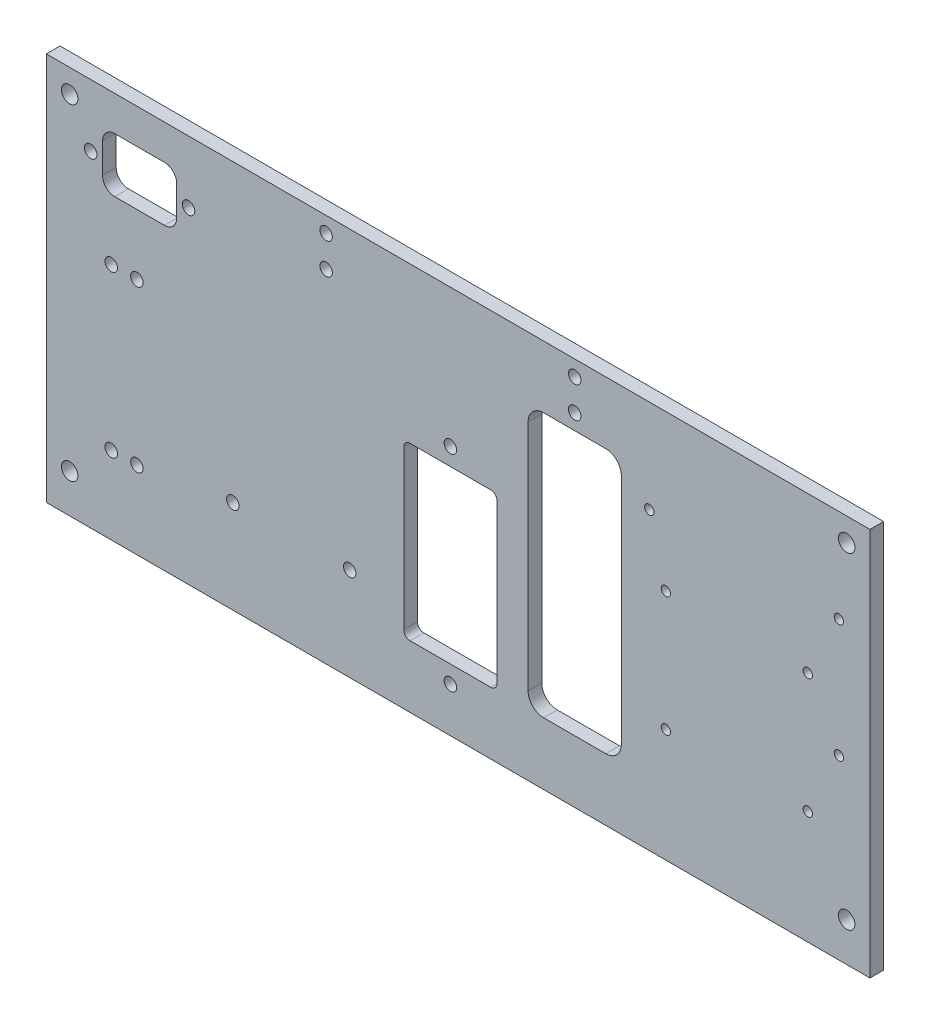
SolidWorks part; units mm, degrees
material "Acrylic (Medium-high impact)"
ref_plane "Front Plane" through (0, 0, 0) normal (0, 0, 1) x (1, 0, 0)
ref_plane "Top Plane" through (0, 0, 0) normal (0, 1, 0) x (1, 0, 0)
ref_plane "Right Plane" through (0, 0, 0) normal (1, 0, 0) x (0, 0, -1)
sketch "Sketch1" plane through (0, 0, 0) normal (0, 0, 1) x (1, 0, 0)
  line L1 (-168.275, 79.375) -> (168.275, 79.375)
  line L2 (-168.275, 79.375) -> (-168.275, -79.375)
  line L3 (-168.275, -79.375) -> (168.275, -79.375)
  line L4 (168.275, 79.375) -> (168.275, -79.375)
  line L5 (-168.275, 79.375) -> (168.275, -79.375) construction
  line L6 (-168.275, -79.375) -> (168.275, 79.375) construction
  point P0 (0, 0)
  dimension "D1" = 158.75
  dimension "D2" = 336.55
extrude "Boss-Extrude1" add sketch "Sketch1" along normal blind 5.588 contours L1 L4 L3 L2
hole_wizard "1/4 Clearance Hole1" positions "Sketch3" profile "Sketch2" hole size "1/4" standard "ANSI Inch" end condition up to next
sketch "Sketch3" plane through (0, 0, 0) normal (0, 0, -1) x (-1, 0, 0)
  line L1 (-158.75, 69.85) -> (158.75, 69.85) construction
  line L2 (-158.75, 69.85) -> (-158.75, -63.5) construction
  line L3 (-158.75, -63.5) -> (158.75, -63.5) construction
  line L4 (158.75, 69.85) -> (158.75, -63.5) construction
  line L5 (168.275, 79.375) -> (-168.275, 79.375) construction
  line L6 (-168.275, 79.375) -> (-168.275, -79.375) construction
  line L10 (168.275, 79.375) -> (168.275, -79.375) construction
  line L11 (168.275, -79.375) -> (-168.275, -79.375) construction
  point P1 (-158.75, 69.85)
  point P2 (158.75, -63.5)
  point P283 (-158.75, -63.5)
  point P284 (158.75, 69.85)
  dimension "D1" = 9.525
  dimension "D2" = 9.525
  dimension "D3" = 9.525
  dimension "D4" = 15.875
sketch "Sketch2" plane through (158.75, 69.85, 0) normal (1, 0, 0) x (0, 1, 0)
  line L0 (0, 0) -> (0, 5.588)
  line L1 (0, 5.588) -> (3.3782, 5.588)
  line L2 (3.3782, 5.588) -> (3.3782, 0)
  line L5 (3.3782, 0) -> (0, 0)
  line L11 (0, -6.35) -> (0, 107.95) construction
  dimension "Thru Hole Dia." = 6.7564
  dimension "Thru Hole Depth" = 5.588
hole_wizard "#6 Clearance Hole1" positions "Sketch6" profile "Sketch7" hole size "#6" standard "ANSI Inch" end condition up to next
sketch "Sketch6" plane through (0, 0, 0) normal (0, 0, -1) x (-1, 0, 0)
  line L1 (-155.575, 41.275) -> (-78.105, 41.275) construction
  line L2 (-155.575, 41.275) -> (-155.575, -6.985) construction
  line L3 (-155.575, -6.985) -> (-78.105, -6.985) construction
  line L4 (-78.105, 41.275) -> (-78.105, -6.985) construction
  line L5 (-168.275, 79.375) -> (-168.275, -79.375) construction
  line L6 (168.275, 79.375) -> (-168.275, 79.375) construction
  point P0 (-155.575, 41.275)
  point P105 (-155.575, -6.985)
  point P106 (-78.105, 41.275)
  dimension "D1" = 77.47
  dimension "D2" = 48.26
  dimension "D3" = 12.7
  dimension "D4" = 38.1
sketch "Sketch7" plane through (155.575, 41.275, 0) normal (1, 0, 0) x (0, 1, 0)
  line L0 (0, 0) -> (0, 5.588)
  line L1 (0, 5.588) -> (1.8986, 5.588)
  line L2 (1.8986, 5.588) -> (1.8986, 0)
  line L5 (1.8986, 0) -> (0, 0)
  line L11 (0, -6.35) -> (0, 107.95) construction
  dimension "Thru Hole Dia." = 3.7973
  dimension "Thru Hole Depth" = 5.588
hole_wizard "#6 Clearance Hole2" positions "Sketch9" profile "Sketch10" hole size "#6" standard "ANSI Inch" end condition up to next
sketch "Sketch9" plane through (0, 0, 0) normal (0, 0, -1) x (-1, 0, 0)
  line L1 (-142.875, 15.875) -> (-84.875, 15.875) construction
  line L2 (-142.875, 15.875) -> (-142.875, -33.125) construction
  line L3 (-142.875, -33.125) -> (-84.875, -33.125) construction
  line L4 (-84.875, 15.875) -> (-84.875, -33.125) construction
  line L5 (-168.275, 79.375) -> (-168.275, -79.375) construction
  line L6 (168.275, 79.375) -> (-168.275, 79.375) construction
  point P0 (-142.875, 15.875)
  point P1 (-84.875, -33.125)
  point P148 (-142.875, -33.125)
  point P149 (-84.875, 15.875)
  dimension "D1" = 58
  dimension "D2" = 49
  dimension "D3" = 25.4
  dimension "D4" = 63.5
sketch "Sketch10" plane through (142.875, 15.875, 0) normal (1, 0, 0) x (0, 1, 0)
  line L0 (0, 0) -> (0, 5.588)
  line L1 (0, 5.588) -> (1.8986, 5.588)
  line L2 (1.8986, 5.588) -> (1.8986, 0)
  line L5 (1.8986, 0) -> (0, 0)
  line L11 (0, -6.35) -> (0, 107.95) construction
  dimension "Thru Hole Dia." = 3.7973
  dimension "Thru Hole Depth" = 5.588
sketch "Sketch11" plane through (0, 0, 0) normal (0, 0, -1) x (-1, 0, 0)
  line L0 (168.275, 79.375) -> (168.275, -79.375) construction
  line L1 (-13.335, 15.875) -> (19.685, 15.875)
  line L2 (-15.875, 13.335) -> (-15.875, -51.435)
  line L3 (-13.335, -53.975) -> (19.685, -53.975)
  line L4 (22.225, 13.335) -> (22.225, -51.435)
  line L5 (168.275, -79.375) -> (-168.275, -79.375) construction
  arc A0 (19.685, 15.875) -> (22.225, 13.335) centre (19.685, 13.335) cw
  arc A1 (19.685, -53.975) -> (22.225, -51.435) centre (19.685, -51.435) ccw
  arc A2 (-15.875, -51.435) -> (-13.335, -53.975) centre (-13.335, -51.435) ccw
  arc A3 (-13.335, 15.875) -> (-15.875, 13.335) centre (-13.335, 13.335) ccw
  point P10 (22.225, 15.875)
  point P15 (-15.875, -53.975)
  point P18 (-15.875, 15.875)
  dimension "D5" = 2.54
  dimension "D1" = 38.1
  dimension "D2" = 69.85
  dimension "D3" = 146.05
  dimension "D4" = 25.4
extrude "Cut-Extrude1" cut sketch "Sketch11" against normal up to next
hole_wizard "#10 Clearance Hole1" positions "Sketch13" profile "Sketch14" hole size "#10" standard "ANSI Inch" end condition up to next
sketch "Sketch13" plane through (0, 0, 0) normal (0, 0, -1) x (-1, 0, 0)
  line L7 (-15.875, -19.05) -> (3.175, -19.05) construction
  line L8 (-15.875, 13.335) -> (-15.875, -51.435) construction
  line L10 (3.175, 23.0187) -> (3.175, -61.1188) construction
  point P12 (3.175, 23.0187)
  point P17 (3.175, -61.1188)
  dimension "D1" = 19.05
  dimension "D2" = 84.1375
sketch "Sketch14" plane through (-3.175, 23.0187, 0) normal (1, 0, 0) x (0, 1, 0)
  line L0 (0, 0) -> (0, 5.588)
  line L1 (0, 5.588) -> (2.5527, 5.588)
  line L2 (2.5527, 5.588) -> (2.5527, 0)
  line L5 (2.5527, 0) -> (0, 0)
  line L11 (0, -6.35) -> (0, 107.95) construction
  dimension "Thru Hole Dia." = 5.1054
  dimension "Thru Hole Depth" = 5.588
sketch "Sketch15" plane through (0, 0, 0) normal (0, 0, -1) x (-1, 0, 0)
  line L0 (-168.275, 79.375) -> (-168.275, -79.375) construction
  line L1 (-60.325, 53.975) -> (-34.925, 53.975)
  line L2 (-66.675, 47.625) -> (-66.675, -47.625)
  line L3 (-60.325, -53.975) -> (-34.925, -53.975)
  line L4 (-28.575, 47.625) -> (-28.575, -47.625)
  line L5 (168.275, 79.375) -> (-168.275, 79.375) construction
  line L6 (168.275, -79.375) -> (-168.275, -79.375) construction
  arc A0 (-34.925, 53.975) -> (-28.575, 47.625) centre (-34.925, 47.625) cw
  arc A1 (-34.925, -53.975) -> (-28.575, -47.625) centre (-34.925, -47.625) ccw
  arc A2 (-66.675, -47.625) -> (-60.325, -53.975) centre (-60.325, -47.625) ccw
  arc A3 (-60.325, 53.975) -> (-66.675, 47.625) centre (-60.325, 47.625) ccw
  point P12 (-28.575, 53.975)
  point P19 (-66.675, 53.975)
  dimension "D5" = 6.35
  dimension "D1" = 101.6
  dimension "D2" = 25.4
  dimension "D3" = 25.4
  dimension "D4" = 38.1
extrude "Cut-Extrude2" cut sketch "Sketch15" against normal up to next
hole_wizard "#10 Clearance Hole3" positions "Sketch17" profile "Sketch18" hole size "#10" standard "ANSI Inch" end condition up to next
sketch "Sketch17" plane through (0, 0, 0) normal (0, 0, -1) x (-1, 0, 0)
  line L4 (131.2799, 18.0848) -> (141.7701, 18.0848) construction
  line L7 (131.2799, -47.625) -> (141.7701, -47.625) construction
  line L9 (136.525, 18.0848) -> (136.525, -47.625) construction
  line L10 (168.275, 79.375) -> (168.275, -79.375) construction
  line L11 (168.275, -79.375) -> (-168.275, -79.375) construction
  point P0 (131.2799, 18.0848)
  point P1 (131.2799, -47.625)
  point P17 (141.7701, 18.0848)
  point P23 (141.7701, -47.625)
  dimension "D1" = 10.4902
  dimension "D2" = 65.7098
  dimension "D3" = 31.75
  dimension "D4" = 31.75
sketch "Sketch18" plane through (-131.2799, 18.0848, 0) normal (1, 0, 0) x (0, 1, 0)
  line L0 (0, 0) -> (0, 5.588)
  line L1 (0, 5.588) -> (2.5527, 5.588)
  line L2 (2.5527, 5.588) -> (2.5527, 0)
  line L5 (2.5527, 0) -> (0, 0)
  line L11 (0, -6.35) -> (0, 107.95) construction
  dimension "Thru Hole Dia." = 5.1054
  dimension "Thru Hole Depth" = 5.588
hole_wizard "#10 Clearance Hole2" positions "Sketch20" profile "Sketch21" hole size "#10" standard "ANSI Inch" end condition up to next
sketch "Sketch20" plane through (0, 0, 0) normal (0, 0, -1) x (-1, 0, 0)
  line L2 (-47.625, 73.025) -> (53.975, 73.025) construction
  line L3 (-47.625, 73.025) -> (-47.625, 60.325) construction
  line L4 (-47.625, 60.325) -> (53.975, 60.325) construction
  line L5 (53.975, 73.025) -> (53.975, 60.325) construction
  line L6 (168.275, 79.375) -> (168.275, -79.375) construction
  line L7 (168.275, 79.375) -> (-168.275, 79.375) construction
  point P3 (-47.625, 73.025)
  point P4 (53.975, 60.325)
  point P287 (-47.625, 60.325)
  point P288 (53.975, 73.025)
  dimension "D1" = 101.6
  dimension "D2" = 12.7
  dimension "D3" = 114.3
  dimension "D4" = 6.35
sketch "Sketch21" plane through (47.625, 73.025, 0) normal (1, 0, 0) x (0, 1, 0)
  line L0 (0, 0) -> (0, 5.588)
  line L1 (0, 5.588) -> (2.5527, 5.588)
  line L2 (2.5527, 5.588) -> (2.5527, 0)
  line L5 (2.5527, 0) -> (0, 0)
  line L11 (0, -6.35) -> (0, 107.95) construction
  dimension "Thru Hole Dia." = 5.1054
  dimension "Thru Hole Depth" = 5.588
hole_wizard "#10 Clearance Hole4" positions "Sketch23" profile "Sketch22" hole size "#10" standard "ANSI Inch" end condition up to next
sketch "Sketch23" plane through (0, 0, 0) normal (0, 0, -1) x (-1, 0, 0)
  line L0 (44.323, -41.275) -> (92.075, -41.275) construction
  line L6 (168.275, -79.375) -> (-168.275, -79.375) construction
  line L7 (168.275, 79.375) -> (168.275, -79.375) construction
  point P1 (44.323, -41.275)
  point P2 (92.075, -41.275)
  dimension "D1" = 47.752
  dimension "D2" = 38.1
  dimension "D3" = 76.2
sketch "Sketch22" plane through (-44.323, -41.275, 0) normal (1, 0, 0) x (0, 1, 0)
  line L0 (0, 0) -> (0, 5.588)
  line L1 (0, 5.588) -> (2.5527, 5.588)
  line L2 (2.5527, 5.588) -> (2.5527, 0)
  line L5 (2.5527, 0) -> (0, 0)
  line L11 (0, -6.35) -> (0, 107.95) construction
  dimension "Thru Hole Dia." = 5.1054
  dimension "Thru Hole Depth" = 5.588
sketch "Sketch24" plane through (0, 0, 0) normal (0, 0, -1) x (-1, 0, 0)
  line L0 (130.175, 65.125) -> (130.175, 42.825) construction
  line L1 (120.025, 65.125) -> (140.325, 65.125)
  line L2 (115.025, 60.125) -> (115.025, 47.825)
  line L3 (120.025, 42.825) -> (140.325, 42.825)
  line L4 (145.325, 60.125) -> (145.325, 47.825)
  line L5 (150.175, 53.975) -> (110.175, 53.975) construction
  line L6 (168.275, 79.375) -> (-168.275, 79.375) construction
  line L7 (168.275, 79.375) -> (168.275, -79.375) construction
  circle A0 centre (110.175, 53.975) radius 2.5527
  circle A1 centre (150.175, 53.975) radius 2.5527
  arc A2 (140.325, 65.125) -> (145.325, 60.125) centre (140.325, 60.125) cw
  arc A3 (140.325, 42.825) -> (145.325, 47.825) centre (140.325, 47.825) ccw
  arc A4 (115.025, 47.825) -> (120.025, 42.825) centre (120.025, 47.825) ccw
  arc A5 (120.025, 65.125) -> (115.025, 60.125) centre (120.025, 60.125) ccw
  point P9 (130.175, 53.975)
  point P13 (145.325, 65.125)
  point P16 (145.325, 42.825)
  point P21 (115.025, 65.125)
  dimension "D4" = 5.1054
  dimension "D5" = 5
  dimension "D1" = 30.3
  dimension "D2" = 22.3
  dimension "D3" = 40
  dimension "D6" = 25.4
  dimension "D7" = 38.1
extrude "Cut-Extrude3" cut sketch "Sketch24" against normal up to next
